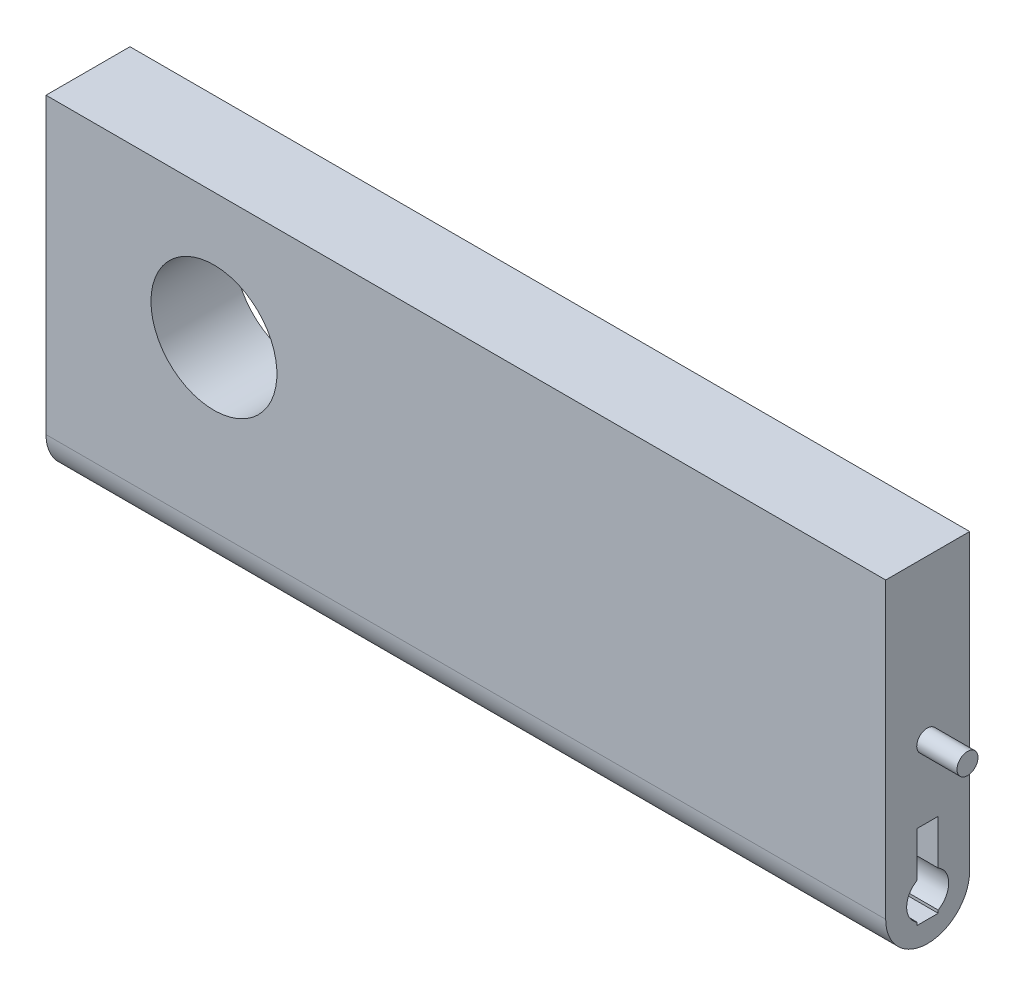
SolidWorks part; units mm, degrees
ref_plane "Front Plane" through (0, 0, 0) normal (0, 0, 1) x (1, 0, 0)
ref_plane "Top Plane" through (0, 0, 0) normal (0, 1, 0) x (1, 0, 0)
ref_plane "Right Plane" through (0, 0, 0) normal (1, 0, 0) x (0, 0, -1)
sketch "Sketch1" plane through (0, 0, 0) normal (0, 0, 1) x (1, 0, 0)
  line L1 (34.925, -12.7) -> (-34.925, -12.7)
  line L2 (34.925, -12.7) -> (34.925, 12.7)
  line L3 (34.925, 12.7) -> (-34.925, 12.7)
  line L4 (-34.925, -12.7) -> (-34.925, 12.7)
  line L5 (34.925, -12.7) -> (-34.925, 12.7) construction
  line L6 (34.925, 12.7) -> (-34.925, -12.7) construction
  line L7 (34.925, -12.7) -> (28.575, -12.7)
  line L8 (34.925, -12.7) -> (34.925, 12.7)
  line L9 (34.925, 12.7) -> (28.575, 12.7)
  line L10 (28.575, -12.7) -> (28.575, 12.7)
  point P0 (0, 0)
  dimension "D1" = 25.4
  dimension "D2" = 69.85
  dimension "D3" = 6.35
  dimension "D4" = 25.4
extrude "Boss-Extrude1" add sketch "Sketch1" along normal blind 6.35 contours L1 L10 L9 L2 L3 L4 region at (-3.175, 0, 0)
sketch "Sketch3" plane through (28.575, 0, 6.35) normal (1, 0, 0) x (0, 0, -1)
  line L2 (0, -12.7) -> (6.35, -12.7) construction
  line L3 (6.35, -12.7) -> (6.35, 12.7) construction
  circle A0 centre (3.175, -9.525) radius 1.5875
  point P2 (0, 0)
  dimension "D2" = 3.175
  dimension "D1" = 3.175
  dimension "D3" = 3.175
extrude "Cut-Extrude2" cut sketch "Sketch3" against normal through all
fillet "Fillet1" radius 3.175 2 edges at (-3.175, -12.7, 0) (-3.175, -12.7, 6.35)
sketch "Sketch4" plane through (0, 0, 0) normal (0, 0, -1) x (-1, 0, 0)
  line L2 (-28.575, 12.7) -> (34.925, 12.7) construction
  line L4 (34.925, -9.525) -> (34.925, 12.7) construction
  circle A2 centre (22.225, 3.175) radius 4.7625
  point P6 (34.925, -5.9751)
  point P7 (40.4575, 2.057)
  dimension "D1" = 9.525
  dimension "D2" = 9.525
  dimension "D3" = 12.7
extrude "Cut-Extrude3" cut sketch "Sketch4" against normal through all
sketch "Sketch5" plane through (28.575, 0, 0) normal (1, 0, 0) x (0, 0, -1)
  line L1 (-3.9688, -11.1125) -> (-2.3813, -11.1125)
  line L2 (-3.9688, -11.1125) -> (-3.9688, -4.7625)
  line L3 (-3.9688, -4.7625) -> (-2.3813, -4.7625)
  line L4 (-2.3813, -11.1125) -> (-2.3813, -4.7625)
  line L5 (-3.9688, -11.1125) -> (-2.3813, -4.7625) construction
  line L6 (-3.9688, -4.7625) -> (-2.3813, -11.1125) construction
  circle A0 centre (-3.175, -9.525) radius 1.5875 construction
  point P0 (-3.175, -7.9375)
  dimension "D1" = 1.5875
  dimension "D2" = 3.175
extrude "Cut-Extrude4" cut sketch "Sketch5" against normal blind 3.175
sketch "Sketch6" plane through (28.575, 0, 0) normal (1, 0, 0) x (0, 0, -1)
  circle A0 centre (-3.2095, 0.635) radius 0.7937
  arc A1 (-3.9688, -8.1502) -> (-3.9688, -10.8998) centre (-3.175, -9.525) ccw construction
  dimension "D1" = 10.16
  dimension "D2" = 1.5875
extrude "Boss-Extrude2" add sketch "Sketch6" along normal blind 3.048
